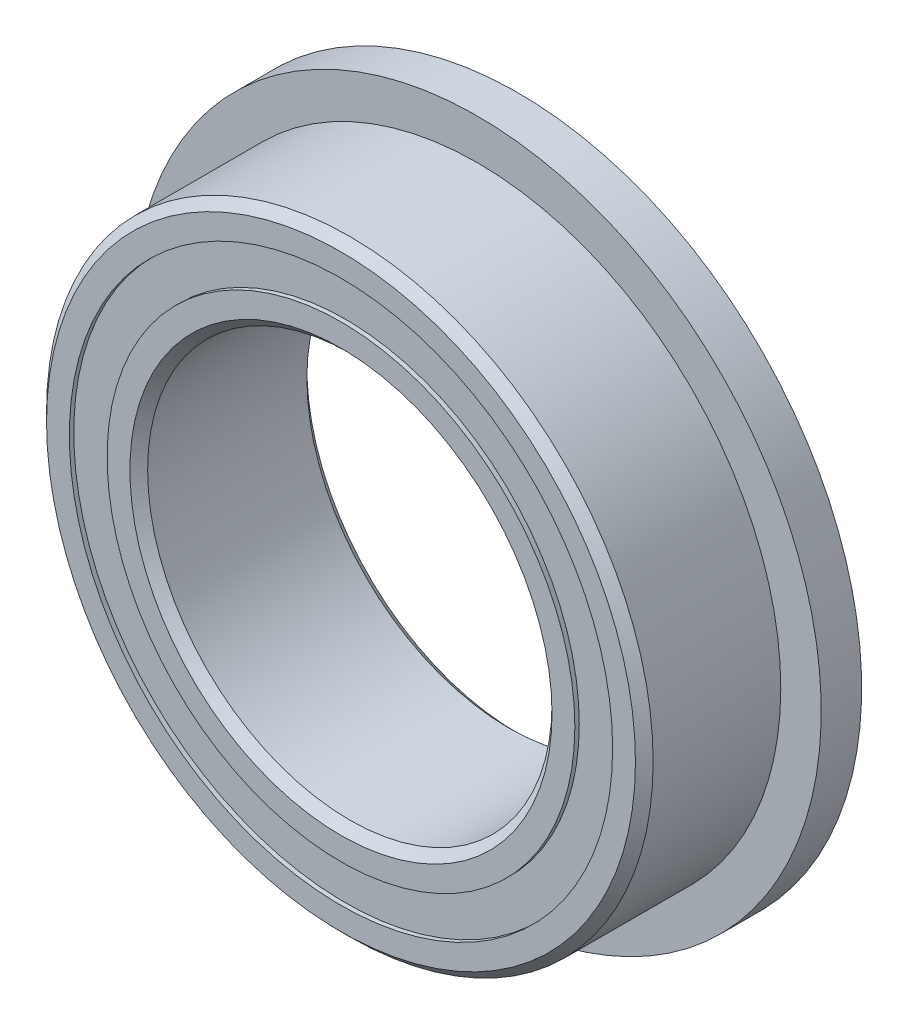
SolidWorks part; units mm, degrees
material "Stainless Steel (ferritic)"
ref_plane "Front Plane" through (0, 0, 0) normal (0, 0, 1) x (1, 0, 0)
ref_plane "Top Plane" through (0, 0, 0) normal (0, 1, 0) x (1, 0, 0)
ref_plane "Right Plane" through (0, 0, 0) normal (1, 0, 0) x (0, 0, -1)
sketch "Sketch1" plane through (0, 0, 0) normal (1, 0, 0) x (0, 0, -1)
  line L0 (-1.75, 0) -> (1.75, 0) construction
  line L1 (0, 6) -> (0, -6) construction
  line L2 (1.575, 6) -> (-1.575, 6)
  line L3 (-1.575, 6) -> (-1.75, 5.825)
  line L4 (-1.75, 5.825) -> (-1.75, 5.3736)
  line L5 (-1.75, 5.3736) -> (-0.7778, 5.3736)
  line L6 (1.75, 5.3736) -> (0.7778, 5.3736)
  line L7 (1.75, 5.825) -> (1.75, 5.3736)
  line L8 (1.575, 6) -> (1.75, 5.825)
  line L9 (0, 6) -> (0, 5) construction
  line L10 (0, 5) -> (0, 4) construction
  arc A0 (-0.7778, 5.3736) -> (0.7778, 5.3736) centre (0, 5) cw
  point P14 (0, 4)
  dimension "Width" = 3.5
  dimension "OD" = 12
  dimension "D1" = 45
  dimension "D2" = 0.175
  dimension "Shaft Dia" = 8
  dimension "D3" = 1.5556
  dimension "D4" = 0.3736
revolve "Revolve1" add sketch "Sketch1" angle 360 about L0
sketch "Sketch3" plane through (0, 0, 0) normal (1, 0, 0) x (0, 0, -1)
  line L0 (-1.75, 4.6264) -> (-0.7778, 4.6264)
  line L1 (0, 6) -> (0, -6) construction
  line L2 (-1.75, 5.825) -> (-1.75, 5.3736) construction
  line L3 (-1.75, 4.6264) -> (-1.75, 4.175)
  line L4 (-1.575, 6) -> (-1.75, 5.825) construction
  line L5 (-1.75, 4.175) -> (-1.575, 4)
  line L6 (-1.575, 4) -> (1.575, 4)
  line L7 (1.575, 6) -> (1.575, -6) construction
  line L8 (1.575, 4) -> (1.75, 4.175)
  line L9 (1.75, -5.825) -> (1.75, 5.825) construction
  line L10 (1.75, 4.175) -> (1.75, 4.6264)
  line L11 (1.75, 4.6264) -> (0.7778, 4.6264)
  line L13 (1.575, 6) -> (1.75, 5.825) construction
  arc A0 (0.7778, 5.3736) -> (-0.7778, 5.3736) centre (0, 5) ccw construction
  arc A1 (0.7778, 4.6264) -> (-0.7778, 4.6264) centre (0, 5) cw
revolve "Revolve3" add sketch "Sketch3" angle 360 about L0
sketch "Sketch4" plane through (0, 0, 0) normal (1, 0, 0) x (0, 0, -1)
  line L0 (-0.8629, 5) -> (0.8629, 5)
  arc A2 (-0.8629, 5) -> (0.8629, 5) centre (0, 5) cw
  arc A3 (0.7778, 5.3736) -> (-0.7778, 5.3736) centre (0, 5) ccw construction
revolve "Revolve4" add sketch "Sketch4" angle 360 about L0
ref_axis "Axis1" through (0, 0, -1.75) along (0, 0, 1)
pattern_circular "CirPattern1" count 12 every 30 about axis through (0, 0, -1.75) along (0, 0, 1) of bodies 104
sketch "Sketch5" plane through (0, 0, 0) normal (1, 0, 0) x (0, 0, -1)
  line L0 (-1.75, 5.3736) -> (-0.7778, 5.3736) construction
  line L1 (-1.6625, 5.3736) -> (-0.8629, 5.3736)
  line L2 (-1.6625, 5.3736) -> (-1.6625, 4.6264)
  line L3 (-1.6625, 4.6264) -> (-0.8629, 4.6264)
  line L4 (-0.8629, 5.3736) -> (-0.8629, 4.6264)
  line L5 (-1.75, 4.6264) -> (-0.7778, 4.6264) construction
  line L6 (1.75, 5.3736) -> (0.7778, 5.3736) construction
  line L7 (1.6625, 5.3736) -> (0.8629, 5.3736)
  line L8 (1.6625, 5.3736) -> (1.6625, 4.6264)
  line L9 (1.6625, 4.6264) -> (0.8629, 4.6264)
  line L10 (0.8629, 5.3736) -> (0.8629, 4.6264)
  line L11 (1.75, 4.6264) -> (0.7778, 4.6264) construction
  line L12 (-1.575, 6) -> (-1.75, 5.825) construction
  point P18 (-1.6625, 5.9125)
revolve "Revolve5" add sketch "Sketch5" angle 360 about L0
sketch "Sketch6" plane through (0, 0, 0) normal (1, 0, 0) x (0, 0, -1)
  line L0 (1.75, 0) -> (-1.75, 0) construction
  line L1 (1.75, 5.3736) -> (0.95, 5.3736)
  line L2 (1.75, 5.3736) -> (1.75, 6.8)
  line L3 (1.75, 6.8) -> (0.95, 6.8)
  line L4 (0.95, 5.3736) -> (0.95, 6.8)
  dimension "Th" = 0.8
  dimension "Flange OD" = 13.6
revolve "Revolve6" add sketch "Sketch6" angle 360 about L0
equation "\"D2@Sketch1\" = \"Width@Sketch1\"*.05"
equation "\"D3@Sketch1\" = \"Width@Sketch1\"/2.25"
equation "\"D4@Sketch1\" = (((\"OD@Sketch1\"-\"Width@Sketch1\")/2)/3.25)/3.5"
equation "\"D2@CirPattern1\" = 360/\"Balls@CirPattern1\""
